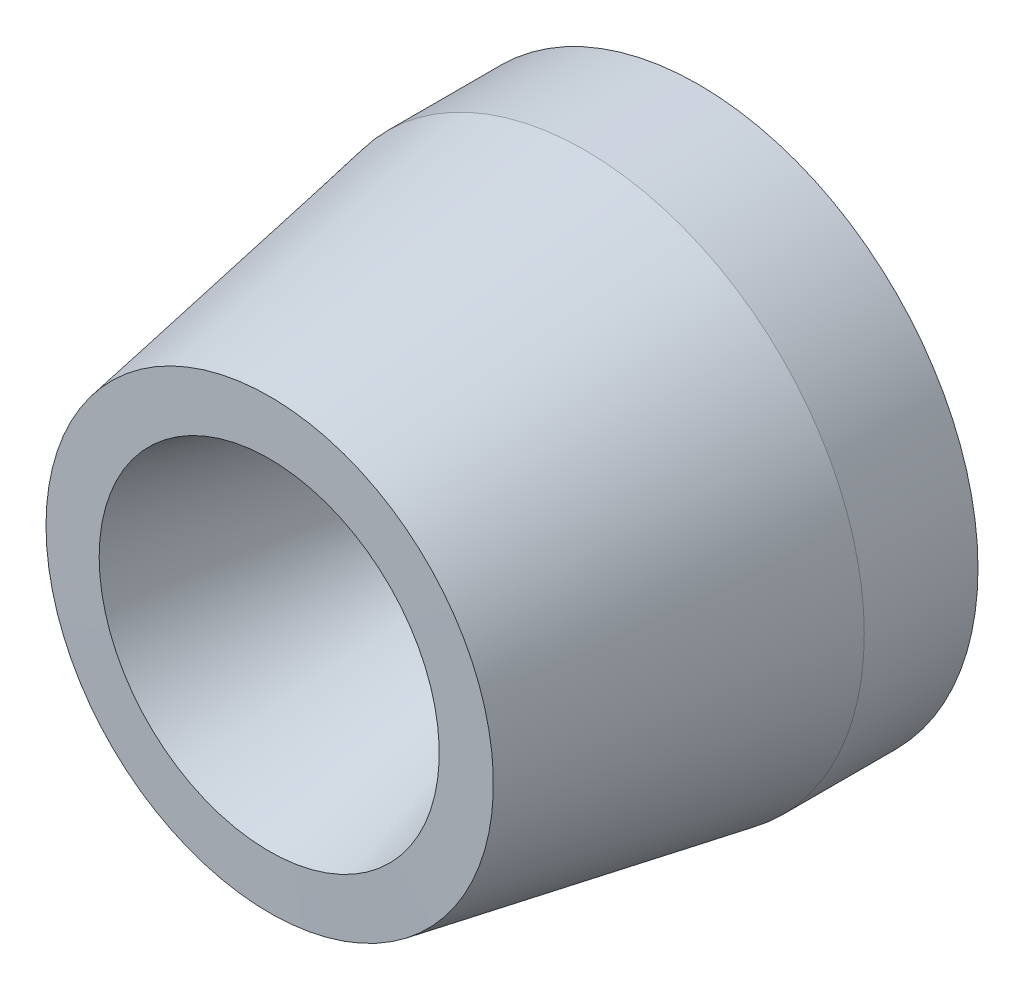
SolidWorks part; units mm, degrees
material "C (Graphite)"
ref_plane "Front Plane" through (0, 0, 0) normal (0, 0, 1) x (1, 0, 0)
ref_plane "Top Plane" through (0, 0, 0) normal (0, 1, 0) x (1, 0, 0)
ref_plane "Right Plane" through (0, 0, 0) normal (1, 0, 0) x (0, 0, -1)
sketch "Sketch1" plane through (0, 0, 0) normal (0, 1, 0) x (1, 0, 0)
  line L3 (40.2808, 69.9382) -> (30.6211, 69.85)
  line L4 (30.6211, 69.85) -> (17.145, 120.1433)
  line L5 (50.292, 126.7147) -> (50.292, 147.194)
  line L6 (40.2808, 69.9382) -> (50.292, 126.7147)
  line L7 (50.292, 126.7147) -> (50.292, 147.194)
  line L8 (40.2808, 69.9382) -> (50.292, 126.7147)
  line L9 (17.145, 120.1433) -> (17.145, 127.7633)
  line L10 (17.145, 127.7633) -> (50.292, 147.194)
  dimension "D1" = 0.508
ref_axis "Axis1" through (0, 0, -91.44) along (0, 0, 1)
revolve "Revolve1" add sketch "Sketch1" angle 360 about axis through (0, 0, -91.44) along (0, 0, 1)
fillet "Fillet1" radius 3.81 2 edges at (-17.145, 0, -127.7633) (-17.145, 0, -120.1433)
